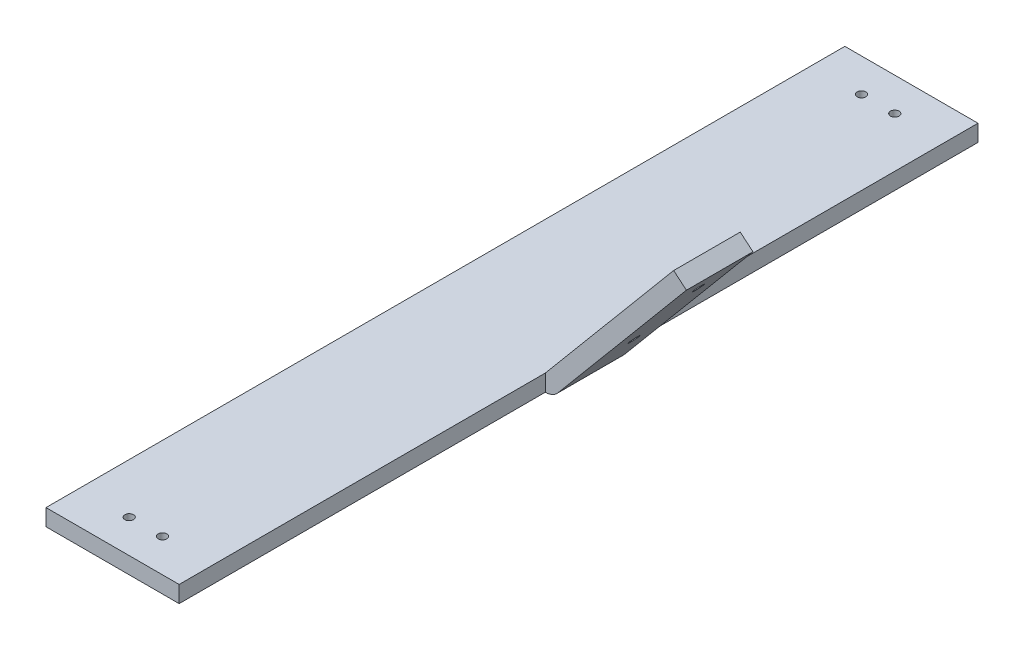
SolidWorks part; units mm, degrees
note: The reader was unsure of these and kept them because the rebuilt part matched: shared geometry of "Sketch1<7>".
ref_plane "Front Plane" through (0, 0, 0) normal (0, 0, 1) x (1, 0, 0)
ref_plane "Top Plane" through (0, 0, 0) normal (0, 1, 0) x (1, 0, 0)
ref_plane "Right Plane" through (0, 0, 0) normal (1, 0, 0) x (0, 0, -1)
sketch "Sketch1" plane through (0, 0, 0) normal (0, 0, 1) x (1, 0, 0)
  line L0 (0, 0) -> (50.8, 0)
  line L1 (50.8, 0) -> (99.7804, 58.3726)
  line L2 (0, 0) -> (0, -6.35)
  line L3 (0, -6.35) -> (50.8, -6.35)
  line L4 (50.8, -6.35) -> (50.8, 0)
  line L5 (55.6644, -4.0817) -> (104.6448, 54.2909)
  line L6 (99.7804, 58.3726) -> (104.6448, 54.2909)
  line L7 (55.6644, -4.0817) -> (50.8, 0)
  arc A0 (50.8, -6.35) -> (55.6644, -4.0817) centre (50.8, 0) ccw
  dimension "D1" = 50.8
  dimension "D2" = 6.35
  dimension "D3" = 76.2
  dimension "D4" = 130
extrude "Boss-Extrude1" add sketch "Sketch1" along normal blind 304.8 from offset 152.4 contours L3 L4 L0 L2 offset against normal yes
extrude "Boss-Extrude2" add sketch "Sketch1<7>" along normal blind 25.4 from offset 12.7 offset against normal yes
sketch "Sketch1<7>" plane through (0, 0, 0) normal (0, 0, 1) x (1, 0, 0) same geometry as "Sketch1"
sketch "Sketch2" plane through (0, 0, 0) normal (0, 1, 0) x (1, 0, 0)
  line L0 (0, -152.4) -> (50.8, -152.4) construction
  line L1 (19.05, -139.7) -> (31.75, -139.7) construction
  line L2 (50.8, 0) -> (0, 0) construction
  line L3 (50.8, -12.7) -> (50.8, 12.7) construction
  line L4 (19.05, 139.7) -> (31.75, 139.7) construction
  circle A0 centre (19.05, -139.7) radius 1.651
  circle A1 centre (31.75, -139.7) radius 1.651
  circle A2 centre (31.75, 139.7) radius 1.651
  circle A3 centre (19.05, 139.7) radius 1.651
  point P6 (25.4, -139.7)
  point P7 (25.4, -139.7)
  point P8 (25.4, -152.4)
  point P9 (25.4, -127)
  point P19 (25.4, 127)
  point P20 (25.4, 152.4)
  point P21 (25.4, 139.7)
  dimension "D1" = 12.7
  dimension "D2" = 3.302
  dimension "D3" = 3.302
  dimension "D4" = 12.7
extrude "Cut-Extrude2" cut sketch "Sketch2" against normal blind 25.4
sketch "Sketch3" plane through (29.8107, -25.0141, 0) normal (-0.766, 0.6428, 0) x (0.6428, 0.766, 0)
  line L1 (108.8536, -12.7) -> (108.8536, 12.7) construction
  circle A0 centre (96.1536, 0) radius 1.9304
  circle A1 centre (58.0536, 0) radius 1.9304
  dimension "D1" = 3.8608
  dimension "D2" = 3.8608
  dimension "D3" = 38.1
  dimension "D4" = 12.7
extrude "Cut-Extrude4" cut sketch "Sketch3" against normal blind 25.4
equation "\"robot-width\"= 12"
